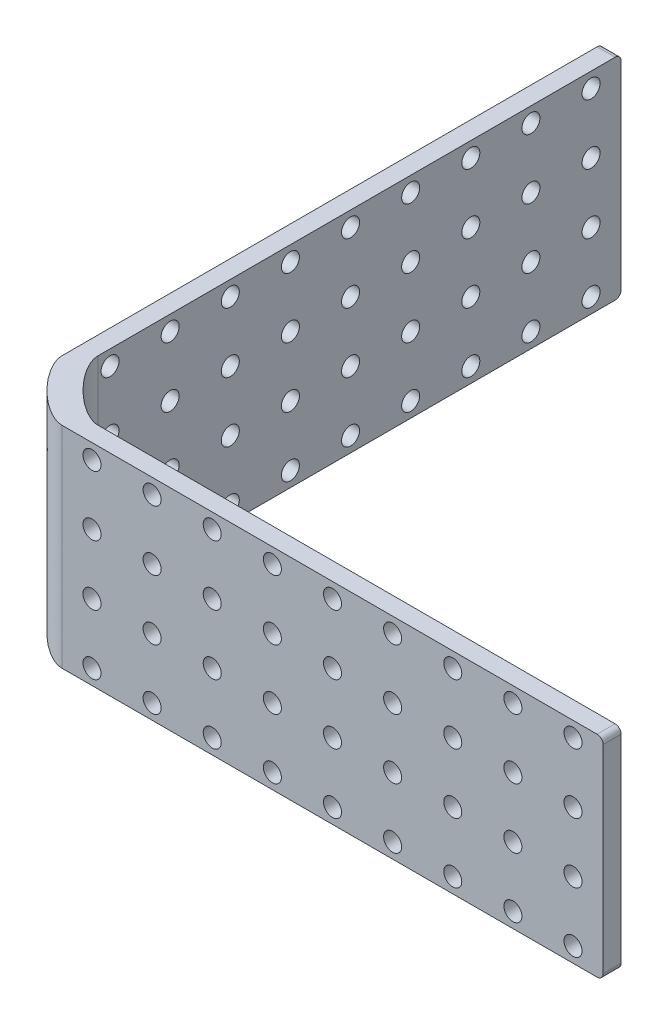
SolidWorks part; units mm, degrees
ref_plane "Plan de face" through (0, 0, 0) normal (0, 0, 1) x (1, 0, 0)
ref_plane "Plan de dessus" through (0, 0, 0) normal (0, 1, 0) x (1, 0, 0)
ref_plane "Plan de droite" through (0, 0, 0) normal (1, 0, 0) x (0, 0, -1)
sketch "Esquisse1" plane through (0, 0, 0) normal (0, 0, 1) x (1, 0, 0)
  line L1 (0, 0) -> (100, 0)
  line L2 (0, 0) -> (0, 35)
  line L3 (0, 35) -> (100, 35)
  line L4 (100, 0) -> (100, 35)
  dimension "D1" = 100
  dimension "D2" = 35
extrude "Boss.-Extru.1" add sketch "Esquisse1" along normal blind 3
sketch "Esquisse2" plane through (0, 0, 3) normal (0, 0, 1) x (1, 0, 0)
  line L0 (100, 35) -> (0, 35) construction
  line L1 (100, 0) -> (100, 35) construction
  circle A0 centre (95, 32.5) radius 1.5
  circle A1 centre (85, 32.5) radius 1.5
  circle A2 centre (75, 32.5) radius 1.5
  circle A3 centre (65, 32.5) radius 1.5
  circle A4 centre (55, 32.5) radius 1.5
  circle A5 centre (45, 32.5) radius 1.5
  circle A6 centre (35, 32.5) radius 1.5
  circle A7 centre (25, 32.5) radius 1.5
  circle A8 centre (15, 32.5) radius 1.5
  circle A10 centre (85, 22.5) radius 1.5
  circle A11 centre (75, 22.5) radius 1.5
  circle A12 centre (65, 22.5) radius 1.5
  circle A13 centre (55, 22.5) radius 1.5
  circle A14 centre (45, 22.5) radius 1.5
  circle A15 centre (35, 22.5) radius 1.5
  circle A16 centre (25, 22.5) radius 1.5
  circle A17 centre (15, 22.5) radius 1.5
  circle A19 centre (85, 12.5) radius 1.5
  circle A20 centre (75, 12.5) radius 1.5
  circle A21 centre (65, 12.5) radius 1.5
  circle A22 centre (55, 12.5) radius 1.5
  circle A23 centre (45, 12.5) radius 1.5
  circle A24 centre (35, 12.5) radius 1.5
  circle A25 centre (25, 12.5) radius 1.5
  circle A26 centre (15, 12.5) radius 1.5
  circle A28 centre (85, 2.5) radius 1.5
  circle A29 centre (75, 2.5) radius 1.5
  circle A30 centre (65, 2.5) radius 1.5
  circle A31 centre (55, 2.5) radius 1.5
  circle A32 centre (45, 2.5) radius 1.5
  circle A33 centre (35, 2.5) radius 1.5
  circle A34 centre (25, 2.5) radius 1.5
  circle A35 centre (15, 2.5) radius 1.5
  circle A37 centre (95, 22.5) radius 1.5
  circle A38 centre (95, 12.5) radius 1.5
  circle A39 centre (95, 2.5) radius 1.5
  circle A40 centre (5, 32.5) radius 1.5 [skipped]
  circle A41 centre (5, 22.5) radius 1.5 [skipped]
  circle A42 centre (5, 12.5) radius 1.5 [skipped]
  circle A43 centre (5, 2.5) radius 1.5 [skipped]
  dimension "D1" = 2.5
  dimension "D2" = 3
  dimension "D3" = 5
  dimension "D4" = 10
  dimension "D5" = 4
extrude "Enlèv. mat.-Extru.1" cut sketch "Esquisse2" against normal blind 3
sketch "Esquisse5" plane through (0, 0, 0) normal (-1, 0, 0) x (0, 0, 1)
  line L0 (3, 0) -> (0, 0) construction
  line L1 (3, 35) -> (-97, 35)
  line L2 (3, 35) -> (3, 0)
  line L3 (3, 0) -> (-97, 0)
  line L4 (-97, 35) -> (-97, 0)
  dimension "D1" = 100
  dimension "D2" = 0
extrude "Boss.-Extru.2" add sketch "Esquisse5" against normal blind 3
sketch "Esquisse6" plane through (3, 0, 0) normal (1, 0, 0) x (0, 0, -1)
  line L0 (0, 35) -> (97, 35) construction
  line L1 (97, 35) -> (97, 0) construction
  circle A0 centre (92, 32.5) radius 1.5
  circle A1 centre (82, 32.5) radius 1.5
  circle A2 centre (72, 32.5) radius 1.5
  circle A3 centre (62, 32.5) radius 1.5
  circle A4 centre (52, 32.5) radius 1.5
  circle A5 centre (42, 32.5) radius 1.5
  circle A6 centre (32, 32.5) radius 1.5
  circle A7 centre (22, 32.5) radius 1.5
  circle A8 centre (12, 32.5) radius 1.5
  circle A9 centre (82, 22.5) radius 1.5
  circle A10 centre (72, 22.5) radius 1.5
  circle A11 centre (62, 22.5) radius 1.5
  circle A12 centre (52, 22.5) radius 1.5
  circle A13 centre (42, 22.5) radius 1.5
  circle A14 centre (32, 22.5) radius 1.5
  circle A15 centre (22, 22.5) radius 1.5
  circle A16 centre (12, 22.5) radius 1.5
  circle A17 centre (82, 12.5) radius 1.5
  circle A18 centre (72, 12.5) radius 1.5
  circle A19 centre (62, 12.5) radius 1.5
  circle A20 centre (52, 12.5) radius 1.5
  circle A21 centre (42, 12.5) radius 1.5
  circle A22 centre (32, 12.5) radius 1.5
  circle A23 centre (22, 12.5) radius 1.5
  circle A24 centre (12, 12.5) radius 1.5
  circle A25 centre (82, 2.5) radius 1.5
  circle A26 centre (72, 2.5) radius 1.5
  circle A27 centre (62, 2.5) radius 1.5
  circle A28 centre (52, 2.5) radius 1.5
  circle A29 centre (42, 2.5) radius 1.5
  circle A30 centre (32, 2.5) radius 1.5
  circle A31 centre (22, 2.5) radius 1.5
  circle A32 centre (12, 2.5) radius 1.5
  circle A33 centre (92, 22.5) radius 1.5
  circle A34 centre (92, 12.5) radius 1.5
  circle A35 centre (92, 2.5) radius 1.5
  dimension "D1" = 2.5
  dimension "D2" = 5
  dimension "D3" = 3
  dimension "D4" = 9
  dimension "D5" = 4
extrude "Enlèv. mat.-Extru.2" cut sketch "Esquisse6" against normal blind 3
fillet "Congé1" radius 10 2 edges at (0, 17.5, 3) (3, 17.5, 0) conic rho 0.25
fillet "Congé2" radius 1 4 edges at (100, 35, 1.5) (100, 0, 1.5) (1.5, 0, -97) (1.5, 35, -97)
